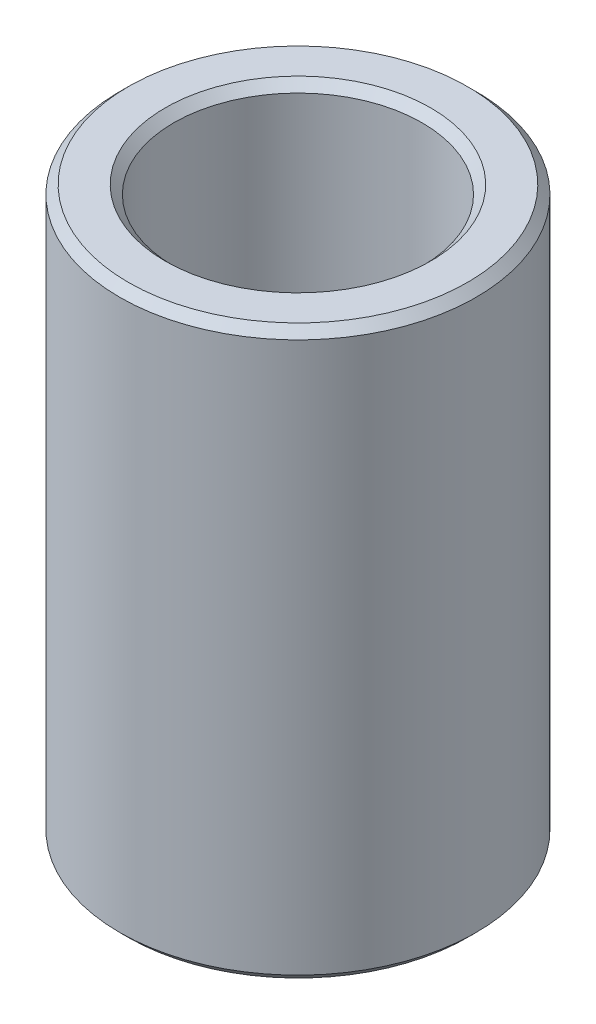
SolidWorks part; units mm, degrees
ref_plane "Front Plane" through (0, 0, 0) normal (0, 0, 1) x (1, 0, 0)
ref_plane "Top Plane" through (0, 0, 0) normal (0, 1, 0) x (1, 0, 0)
ref_plane "Right Plane" through (0, 0, 0) normal (1, 0, 0) x (0, 0, -1)
sketch "Sketch1" plane through (0, 0, 0) normal (0, 1, 0) x (1, 0, 0)
  circle A0 centre (0, 0) radius 52.5
  dimension "SLEEVE_OD" = 105
extrude "Boss-Extrude1" add sketch "Sketch1" along normal blind 167.1376
sketch "Sketch2" plane through (0, 0, 0) normal (0, 1, 0) x (1, 0, 0)
  circle A0 centre (0, 0) radius 36.5787
  dimension "BORE_D" = 73.1573
extrude "Cut-Extrude1" cut sketch "Sketch2" along normal through all
chamfer "Chamfer1" distance 2.5363 angle 45 4 edges at (0, 167.1376, 36.5787) (0, 0, 36.5787) (0, 0, 52.5) (0, 167.1376, 52.5)
